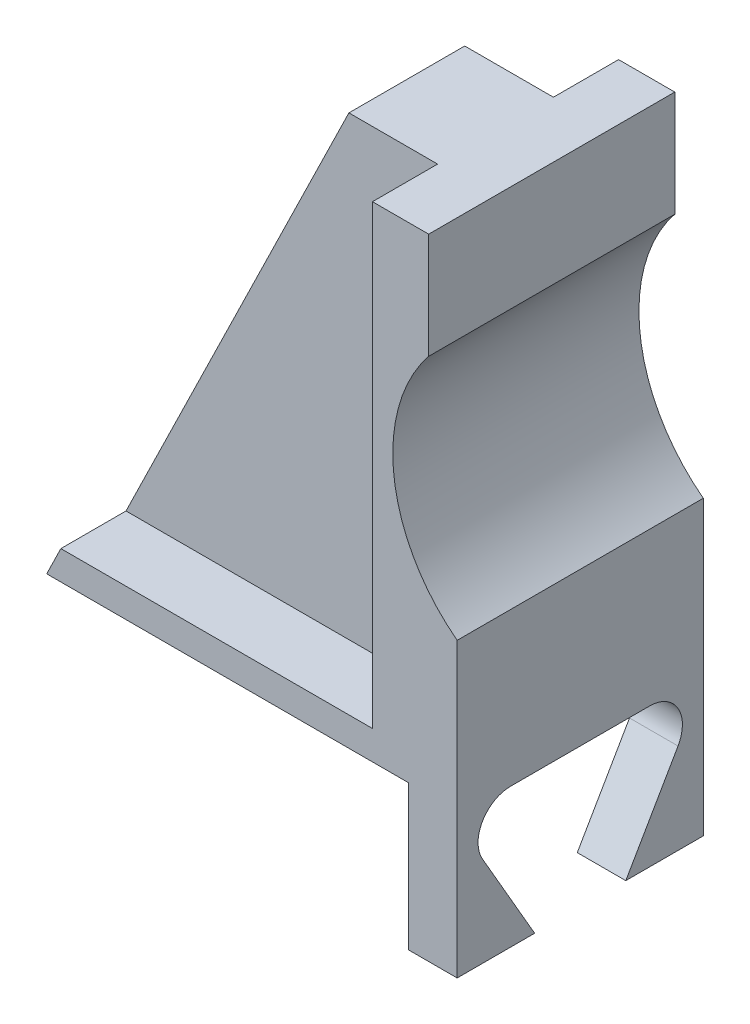
SolidWorks part; units mm, degrees
ref_plane "Front Plane" through (0, 0, 0) normal (0, 0, 1) x (1, 0, 0)
ref_plane "Top Plane" through (0, 0, 0) normal (0, 1, 0) x (1, 0, 0)
ref_plane "Right Plane" through (0, 0, 0) normal (1, 0, 0) x (0, 0, -1)
sketch "Sketch4" plane through (0, 0, 0) normal (0, 0, 1) x (1, 0, 0)
  line L0 (-25, -10) -> (31.7021, -10)
  line L1 (-25, -10) -> (25, -10) construction
  line L2 (-25, -10) -> (-25, 10) construction
  line L3 (-25, 10) -> (25, 10) construction
  line L4 (25, -10) -> (25, 10) construction
  line L5 (-25, -10) -> (25, 10) construction
  line L6 (-25, 10) -> (25, -10) construction
  line L7 (31.7021, -10) -> (31.7021, 30.3986)
  line L8 (27.7654, 62.4074) -> (27.7654, 77.0234)
  line L9 (27.7654, 77.0234) -> (7.7472, 77.0234)
  line L10 (7.7472, 77.0234) -> (-25, 10)
  line L11 (-25, 10) -> (-25, -10)
  arc A0 (27.7654, 62.4074) -> (31.7021, 30.3986) centre (45.316, 48.3194) ccw
  point P0 (0, 0)
  point P10 (-25, 10)
  dimension "D1" = 50
  dimension "D2" = 20
extrude "Boss-Extrude2" add sketch "Sketch4" along normal blind 34
sketch "Sketch5" plane through (0, 0, 34) normal (0, 0, 1) x (1, 0, 0)
  line L0 (-23.0456, 14) -> (7.7472, 77.0234)
  line L1 (-25, -10) -> (25, -10)
  line L2 (-25, -10) -> (-25, 10)
  line L3 (-25, 10) -> (25, 10)
  line L4 (25, -10) -> (25, 10)
  line L5 (7.7472, 77.0234) -> (-25, 10) construction
  line L6 (7.7472, 77.0234) -> (20, 77.0234)
  line L7 (27.7654, 77.0234) -> (7.7472, 77.0234) construction
  line L8 (20, 77.0234) -> (20, 14)
  line L9 (20, 14) -> (-23.0456, 14)
  dimension "D1" = 50
  dimension "D2" = 20
  dimension "D3" = 4
  dimension "D4" = 45
extrude "Cut-Extrude1" cut sketch "Sketch5" against normal blind 9
sketch "Sketch6" plane through (0, 0, 0) normal (0, 0, -1) x (-1, 0, 0)
  line L0 (23.0456, 14) -> (-20, 14)
  line L1 (25, -10) -> (-25, -10)
  line L2 (25, -10) -> (25, 10)
  line L3 (25, 10) -> (-25, 10)
  line L4 (-25, -10) -> (-25, 10)
  line L5 (-7.7472, 77.0234) -> (25, 10) construction
  line L6 (-20, 14) -> (-20, 77.0234)
  line L7 (-27.7654, 77.0234) -> (-7.7472, 77.0234) construction
  line L8 (-20, 77.0234) -> (-7.7472, 77.0234)
  line L9 (-7.7472, 77.0234) -> (23.0456, 14)
  dimension "D1" = 50
  dimension "D2" = 20
  dimension "D3" = 45
  dimension "D4" = 4
extrude "Cut-Extrude2" cut sketch "Sketch6" against normal blind 9
sketch "Sketch7" plane through (0, 0, 9) normal (0, 0, -1) x (-1, 0, 0)
  line L1 (-25, 10) -> (27.0063, 10)
  line L2 (-25, 10) -> (-25, -11.6279)
  line L3 (-25, -11.6279) -> (27.0063, -11.6279)
  line L4 (27.0063, 10) -> (27.0063, -11.6279)
  dimension "D1" = 21.6279
  dimension "D2" = 52.0063
extrude "Cut-Extrude3" cut sketch "Sketch7" against normal through all
sketch "Sketch8" plane through (31.7021, 0, 0) normal (1, 0, 0) x (0, 0, -1)
  line L0 (-26.61, 8) -> (-7.38, 8)
  line L1 (-29.7004, 2.8571) -> (-19.979, -15.4295)
  line L2 (-14.011, -15.4295) -> (-4.2896, 2.8571)
  line L3 (-34, -10) -> (-34, 30.3986) construction
  line L5 (0, -10) -> (0, 30.3986) construction
  line L6 (-34, -10) -> (0, -10) construction
  line L7 (-34, -10) -> (-34, 10) construction
  line L8 (-34, 10) -> (0, 10) construction
  line L9 (0, -10) -> (0, 10) construction
  line L10 (-26.61, 4.5) -> (-7.38, 4.5) construction
  line L11 (-24.295, -13.8431) -> (-10.3108, -13.8431) construction
  arc A3 (-26.61, 8) -> (-29.7004, 2.8571) centre (-26.61, 4.5) ccw
  arc A4 (-7.38, 8) -> (-4.2896, 2.8571) centre (-7.38, 4.5) cw
  arc A5 (-14.011, -15.4295) -> (-19.979, -15.4295) centre (-16.995, -13.8431) cw
  dimension "D1" = 3.5
  dimension "D2" = 3.5
  dimension "D3" = 3.3794
  dimension "D4" = 19.23
  dimension "D5" = 20.71
  dimension "D6" = 20.71
  dimension "D7" = 7.39
  dimension "D8" = 2
  dimension "D9" = 20
sketch "Sketch9" plane through (31.7021, 0, 0) normal (1, 0, 0) x (0, 0, -1)
  line L0 (-26.615, 8.2493) -> (-7.385, 8.2493) construction
  line L1 (-4.3541, 2.999) -> (-13.9691, -13.651) construction
  line L2 (-29.6459, 2.999) -> (-20.0309, -13.651) construction
  line L4 (-34, 30.3986) -> (0, 30.3986) construction
  line L5 (-26.615, 4.7493) -> (-7.385, 4.7493) construction
  line L6 (-17, 4.7493) -> (-17, -11.9007) construction
  line L7 (-34, 10.1993) -> (0, 10.1993) construction
  line L8 (-34, -10) -> (-34, 30.3986) construction
  line L9 (0, -10) -> (0, 30.3986) construction
  line L10 (-26.615, 9.2493) -> (-7.385, 9.2493)
  line L11 (-3.4881, 2.4989) -> (-13.1031, -14.1511)
  line L12 (-30.5119, 2.4989) -> (-20.8969, -14.1511)
  arc A0 (-26.615, 8.2493) -> (-29.6459, 2.999) centre (-26.615, 4.7493) ccw construction
  arc A1 (-4.3541, 2.999) -> (-7.385, 8.2493) centre (-7.385, 4.7493) ccw construction
  arc A2 (-20.0309, -13.651) -> (-13.9691, -13.651) centre (-17, -11.9007) ccw construction
  arc A3 (-29.6459, 2.999) -> (-26.615, 8.2493) centre (-26.615, 4.7493) ccw construction
  arc A4 (-7.385, 8.2493) -> (-4.3541, 2.999) centre (-7.385, 4.7493) ccw construction
  arc A5 (-13.9691, -13.651) -> (-20.0309, -13.651) centre (-17, -11.9007) ccw construction
  arc A6 (-3.4881, 2.4989) -> (-7.385, 9.2493) centre (-7.385, 4.7493) ccw
  arc A7 (-20.8969, -14.1511) -> (-13.1031, -14.1511) centre (-17, -11.9007) ccw
  arc A8 (-26.615, 9.2493) -> (-30.5119, 2.4989) centre (-26.615, 4.7493) ccw
  point P17 (-18.6056, -17.8242)
  point P18 (2.3574, -11.9007)
  point P21 (-17, 30.3986)
  point P22 (-17, -11.5047)
  dimension "D1" = 7
  dimension "D2" = 7
  dimension "D3" = 7
  dimension "D4" = 19.23
  dimension "D5" = 16.65
  dimension "D6" = 1.95
  dimension "D7" = 22.1
  dimension "D8" = 1
extrude "Cut-Extrude4" cut sketch "Sketch9" against normal through all
equation "\"D1@Sketch9\"=3.5*2mm"
